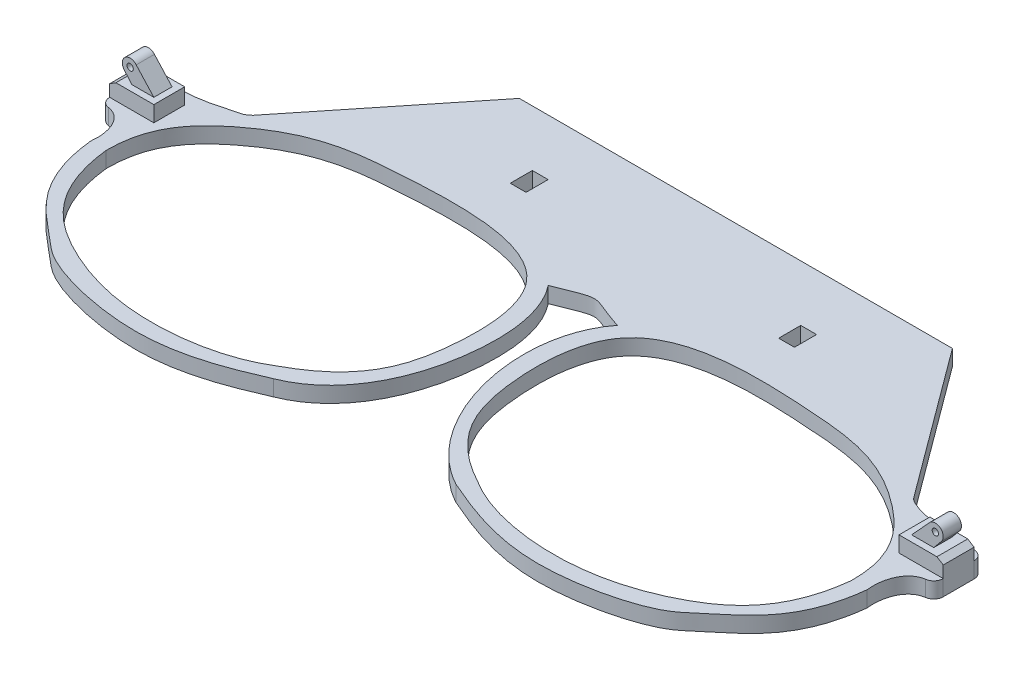
SolidWorks part; units mm, degrees
note: The reader was unsure of these and kept them because the rebuilt part matched: shared geometry of "Sketch2<4>".
ref_plane "Front Plane" through (0, 0, 0) normal (0, 0, 1) x (1, 0, 0)
ref_plane "Top Plane" through (0, 0, 0) normal (0, 1, 0) x (1, 0, 0)
ref_plane "Right Plane" through (0, 0, 0) normal (1, 0, 0) x (0, 0, -1)
sketch "Sketch1" plane through (0, 0, 0) normal (0, 1, 0) x (1, 0, 0)
  line L0 (68, 24.8468) -> (68, 15.0744)
  line L1 (0, 0) -> (-32.1423, -32.1423) construction
  line L2 (-168.3574, 32.8493) -> (-130.8237, 79.6598)
  line L3 (0, 0) -> (-35.1184, -36.1601) construction
  line L4 (-64, -71.9384) -> (-64, 71.9384) construction
  line L5 (-196, 24.8468) -> (-196, 15.0744)
  line L6 (-130.8237, 79.6598) -> (6.322, 79.6598)
  line L7 (6.322, 79.6598) -> (41.0983, 32.6582)
  arc A2 (65.4316, 27.8156) -> (68, 24.8468) centre (65, 24.8468) cw
  arc A3 (65.4316, 12.1056) -> (68, 15.0744) centre (65, 15.0744) ccw
  arc A4 (-193.4316, 27.8156) -> (-196, 24.8468) centre (-193, 24.8468) ccw
  arc A5 (-193.4316, 12.1056) -> (-196, 15.0744) centre (-193, 15.0744) cw
  arc A6 (-168.3574, 32.8493) -> (-170.497, 31.4738) centre (-171.4781, 35.3516) cw
  arc A7 (41.0983, 32.6582) -> (42.497, 31.4738) centre (44.3138, 35.0374) ccw
  ellipse E0 centre (0, 0) end of major axis (54, 0) minor radius 40 construction
  ellipse E1 centre (0, 0) end of major axis (59, 0) minor radius 45 construction
  spline S0 degree 3 poles (54, 0) (54.082, 12.1078) (47.7533, 21.3248) (25.042, 37.943) (-0.849, 40.5662) (-53.6893, 42.3279) (-55.8623, -3.841) (-48.672, -23.2389) (-32.1423, -32.1423) knots 0 0 0 0 0.137497 0.174732 0.372358 0.639272 0.803594 1 1 1 1
  spline S1 degree 3 poles (-32.1423, -32.1423) (-23.5285, -37.5658) (0.7142, -42.5565) (32.9768, -34.6584) (51.8992, -18.9564) (54, 0) knots 0 0 0 0 0.331433 0.662866 1 1 1 1
  spline S2 degree 3 poles (18.8285, 42.647) (12.9467, 44.0184) (6.7661, 44.6433) (0, 45) knots 0.277823 0.277823 0.277823 0.277823 0.372358 0.372358 0.372358 0.372358
  spline S3 degree 3 poles (-35.1184, -36.1601) (-24.3826, -40.8715) (-3.641, -48.7863) (30.6121, -40.4846) (44.4106, -27.7618) (56.7148, -20.6199) (59, 0) knots 0 0 0 0 0.267826 0.508869 0.582087 1 1 1 1
  spline S4 degree 3 poles (-182, 0) (-182.082, 12.1078) (-175.7533, 21.3248) (-153.042, 37.943) (-127.151, 40.5662) (-74.3107, 42.3279) (-72.1377, -3.841) (-79.328, -23.2389) (-95.8577, -32.1423) knots 0 0 0 0 0.137497 0.174732 0.372358 0.639272 0.803594 1 1 1 1
  spline S5 degree 3 poles (-95.8577, -32.1423) (-104.4715, -37.5658) (-128.7142, -42.5565) (-160.9768, -34.6584) (-179.8992, -18.9564) (-182, 0) knots 0 0 0 0 0.331433 0.662866 1 1 1 1
  spline S6 degree 3 poles (-92.8816, -36.1601) (-103.6174, -40.8715) (-124.359, -48.7863) (-158.6121, -40.4846) (-172.4106, -27.7618) (-184.7148, -20.6199) (-187, 0) knots 0 0 0 0 0.267826 0.508869 0.582087 1 1 1 1
  spline S7 degree 3 poles (-187, 0) (-187.082, 12.1078) (-179.1351, 24.4136) (-170.1249, 31.5176) (-169.2211, 32.1953) (-169.2176, 32.198) knots 0 0 0 0 0.137497 0.152781 0.15284 0.15284 0.15284 0.15284
  spline S8 degree 3 poles (-74.9478, 32.9291) (-60.9117, 38.5003) (-66.1681, 37.168) (-53.0522, 32.9291) knots 0 0 0 0 1 1 1 1
  spline S9 degree 3 poles (59, 0) (59.0911, 13.4531) (50.2287, 25.4397) (41.2293, 32.1892) knots 0 0 0 0 0.152774 0.152774 0.152774 0.152774 construction
  spline S10 degree 3 poles (42.497, 31.4738) (45.8415, 29.7687) (53.7989, 28.4929) (62.0724, 28.3039) (65.4316, 27.8156) knots 0.054562 0.054562 0.054562 0.054562 0.473956 0.880924 0.880924 0.880924 0.880924
  spline S11 degree 3 poles (59, 0) (58.3885, 4.231) (59.7531, 11.2801) (65.4316, 12.1056) knots 0 0 0 0 0.91611 0.91611 0.91611 0.91611
  spline S12 degree 3 poles (-170.497, 31.4738) (-174.1364, 30.553) (-181.6558, 28.1124) (-190.0724, 28.3039) (-193.4316, 27.8156) knots 0.054562 0.054562 0.054562 0.054562 0.473956 0.880924 0.880924 0.880924 0.880924
  spline S13 degree 3 poles (-187, 0) (-186.3885, 4.231) (-187.7531, 11.2801) (-193.4316, 12.1056) knots 0 0 0 0 0.91611 0.91611 0.91611 0.91611
  spline S14 degree 3 poles (-92.8816, -36.1601) (-103.6174, -40.8715) (-124.359, -48.7863) (-158.6121, -40.4846) (-172.4106, -27.7618) (-184.7148, -20.6199) (-187, 0) knots 0 0 0 0 0.267826 0.508869 0.582087 1 1 1 1
  spline S15 degree 3 poles (-169.2176, 32.198) (-156.2827, 41.8992) (-141.7818, 44.5218) (-123.0896, 45.2206) (-120.5598, 45.2599) knots 0.152774 0.152774 0.152774 0.152774 0.372358 0.406142 0.406142 0.406142 0.406142
  spline S16 degree 3 poles (-169.2176, 32.198) (-156.2867, 41.8919) (-143.7207, 44.3727) (-128, 45) knots 0.15284 0.15284 0.15284 0.15284 0.372358 0.372358 0.372358 0.372358 construction
  spline S18 degree 3 poles (-120.5598, 45.2599) (-103.1032, 45.5311) (-83.8639, 44.1529) (-74.9478, 32.9291) knots 0.406142 0.406142 0.406142 0.406142 0.639272 0.639272 0.639272 0.639272 construction
  spline S19 degree 3 poles (-74.9478, 32.9291) (-69.0303, 25.48) (-65.2744, -1.5249) (-77.3833, -29.9546) (-92.8816, -36.1601) knots 0.639272 0.639272 0.639272 0.639272 0.783382 1 1 1 1
  spline S20 degree 3 poles (-128, 45) (-117.2328, 45.4296) (-104.9663, 45.8872) (-94.5073, 43.3959) knots 0.372358 0.372358 0.372358 0.372358 0.522707 0.522707 0.522707 0.522707 construction
  spline S21 degree 3 poles (-94.5073, 43.3959) (-86.3985, 41.4644) (-79.4059, 38.541) (-74.9478, 32.9291) knots 0.522707 0.522707 0.522707 0.522707 0.639272 0.639272 0.639272 0.639272 construction
  spline S22 degree 3 poles (0, 45) (-19.1037, 46.0071) (-42.8439, 45.7795) (-53.0522, 32.9291) knots 0.372358 0.372358 0.372358 0.372358 0.639272 0.639272 0.639272 0.639272 construction
  spline S23 degree 3 poles (-53.0522, 32.9291) (-67.2793, 15.0197) (-58.5967, -23.5489) (-35.1184, -36.1601) knots 0.639272 0.639272 0.639272 0.639272 1 1 1 1
  spline S24 degree 3 poles (41.2293, 32.1892) (33.8631, 37.7139) (26.6087, 40.8331) (18.8285, 42.647) knots 0.152774 0.152774 0.152774 0.152774 0.277823 0.277823 0.277823 0.277823 construction
  point P20 (0, 0)
  point P31 (-163.7648, 56.8644)
  point P38 (-64, 0)
  point P39 (20.1026, 73.1706)
  point P48 (-160.8831, 75.8862)
  point P57 (0, 0)
  point P58 (0, 0)
  point P60 (-160.1423, 69.4049)
  point P64 (-160.1423, 69.4049)
  point P65 (32.1423, 69.4049)
  point P66 (0, 0)
  point P67 (0, 0)
  point P68 (0, 0)
  point P69 (0, 0)
  point P70 (68, 19.9606)
  point P71 (0, 0)
  point P72 (21.5132, 70.5256)
  point P73 (-142.6516, 73.1706)
  point P74 (-163.7648, 56.8644)
  point P75 (-143.4386, 71.9384)
  point P76 (0, 0)
  point P78 (13.721, 79.0069)
  point P79 (10.4567, 80.4801)
  point P93 (10.4567, 80.4801)
  point P95 (-138.1769, 73.7841)
  point P96 (0, 0)
  point P97 (0, 0)
  point P98 (-131.4307, 80.4801)
  point P105 (6.322, 79.6598)
  dimension "D4" = 5
  dimension "D7" = 5
  dimension "D5" = 5
  dimension "D17" = 36.6242
  dimension "D9" = 30
  dimension "D19" = 3
  dimension "D20" = 68
  dimension "D25" = 4
  dimension "D16" = 4
  dimension "D1" = 54
  dimension "D2" = 40
  dimension "D3" = 45
  dimension "D6" = 45
  dimension "D10" = 5
  dimension "D11" = 64
  dimension "D14" = 53.0522
  dimension "D15" = 38.8062
  dimension "D18" = 5
  dimension "D21" = 11.4316
  dimension "D22" = 12.1056
  dimension "D23" = 4
extrude "Boss-Extrude2" add sketch "Sketch1" along normal blind 5
ref_plane "Plane1" through (61, 0, 0) normal (1, 0, 0) x (0, 0, -1)
sketch "Sketch2" plane through (61, 0, 0) normal (1, 0, 0) x (0, 0, -1)
  line L0 (15.0744, 5) -> (15.0744, 10)
  line L1 (15.0744, 10) -> (24.8468, 10)
  line L2 (24.8468, 10) -> (24.8468, 5)
  line L4 (15.0744, 0) -> (24.8468, 0)
  line L5 (24.8468, 0) -> (24.8468, 5)
  line L6 (24.8468, 5) -> (15.0744, 5)
  line L7 (15.0744, 5) -> (15.0744, 0)
  line L8 (15.0744, 0) -> (24.8468, 0)
  line L9 (24.8468, 0) -> (24.8468, 5)
  line L10 (24.8468, 5) -> (15.0744, 5)
  line L11 (15.0744, 5) -> (15.0744, 0)
  line L12 (17.0744, 10) -> (22.8468, 10)
  line L13 (17.0744, 10) -> (17.0744, 17)
  line L14 (17.0744, 17) -> (22.8468, 17)
  line L15 (22.8468, 10) -> (22.8468, 17)
  dimension "D2" = 5
  dimension "D3" = 2
  dimension "D4" = 2
  dimension "D5" = 7
  dimension "D1" = 0
extrude "Boss-Extrude3" add sketch "Sketch2" along normal mid plane 14 contours L10 L2 L1 L0 | L13 L12 L15 L14
extrude "Boss-Extrude4" add sketch "Sketch2<4>" along normal mid plane 10 contours L1 L15 L14 L13
sketch "Sketch2<4>" plane through (61, 0, 0) normal (1, 0, 0) x (0, 0, -1) same geometry as "Sketch2"
sketch "Sketch3" plane through (0, 0, -15.0744) normal (0, 0, 1) x (1, 0, 0)
  line L0 (63, 10) -> (63, 5)
  line L1 (66, 10) -> (56, 10) construction
  line L2 (68, 5) -> (54, 5) construction
  line L3 (66, 10) -> (68, 8.7308)
  line L5 (68, 5) -> (68, 10) construction
  line L6 (56, 10) -> (61.7322, 16.2678)
  line L7 (66, 10) -> (66, 17) construction
  line L8 (66, 17) -> (56, 17) construction
  line L9 (63.5, 14.5) -> (61.7322, 16.2678) construction
  line L10 (65.2678, 12.7322) -> (63, 10)
  line L11 (63.5, 14.5) -> (65.2678, 12.7322) construction
  line L16 (56, 17) -> (56, 10)
  line L17 (56, 10) -> (66, 10)
  line L18 (66, 10) -> (66, 17)
  line L19 (66, 17) -> (56, 17)
  line L20 (56, 17) -> (56, 10)
  line L21 (56, 10) -> (66, 10)
  line L22 (66, 10) -> (66, 17)
  line L23 (66, 17) -> (56, 17)
  arc A0 (65.2678, 12.7322) -> (61.5818, 16.1033) centre (63.5, 14.5) ccw
  circle A1 centre (63.5, 14.5) radius 1
  line M4 (68, 5) -> (68, 10)
  line M5 (68, 10) -> (54, 10)
  dimension "D3" = 5
  dimension "D4" = 45
  dimension "D6" = 2
  dimension "D1" = 1.2692
  dimension "D2" = 5
  dimension "D5" = 45
  dimension "D7" = 0
extrude "Cut-Extrude1" cut sketch "Sketch3" against normal through all contours L3 M5 M4 | A0 L23 L20 L6 | A0 L22 L23 | A0 L10 L22 M5 | A1
ref_plane "Plane2" through (-64, 0, 0) normal (1, 0, 0) x (0, 0, -1)
mirror "Mirror1" about plane through (-64, 0, 0) normal (1, 0, 0) of "Boss-Extrude3", "Cut-Extrude1", "Boss-Extrude4"
sketch "Sketch6" plane through (0, 0, 0) normal (0, -1, 0) x (1, 0, 0)
  line L1 (-109, -61.9498) -> (-104, -61.9498)
  line L2 (-109, -61.9498) -> (-109, -54.9498)
  line L3 (-109, -54.9498) -> (-104, -54.9498)
  line L4 (-104, -61.9498) -> (-104, -54.9498)
  line L7 (-64, 71.9384) -> (-64, -71.9384) construction
  line L8 (-64, -12.1) -> (-64, 12.1) construction
  line L9 (-24, -61.9498) -> (-24, -54.9498)
  line L10 (-19, -61.9498) -> (-19, -54.9498)
  line L11 (-19, -54.9498) -> (-24, -54.9498)
  line L12 (-19, -61.9498) -> (-24, -61.9498)
  line L13 (-130.8237, -79.6598) -> (6.322, -79.6598) construction
  line L18 (-129, -69.9498) -> (1, -69.9498) construction
  line L19 (-129, -69.9498) -> (-129, -49.9498) construction
  line L20 (-129, -49.9498) -> (1, -49.9498) construction
  line L21 (1, -69.9498) -> (1, -49.9498) construction
  dimension "D1" = 40
  dimension "D2" = 5
  dimension "7" = 7
  dimension "D3" = 20
  dimension "D4" = 130
  dimension "D5" = 65
  dimension "D6" = 9.71
  dimension "D7" = 5
extrude "Cut-Extrude2" cut sketch "Sketch6" against normal through all
